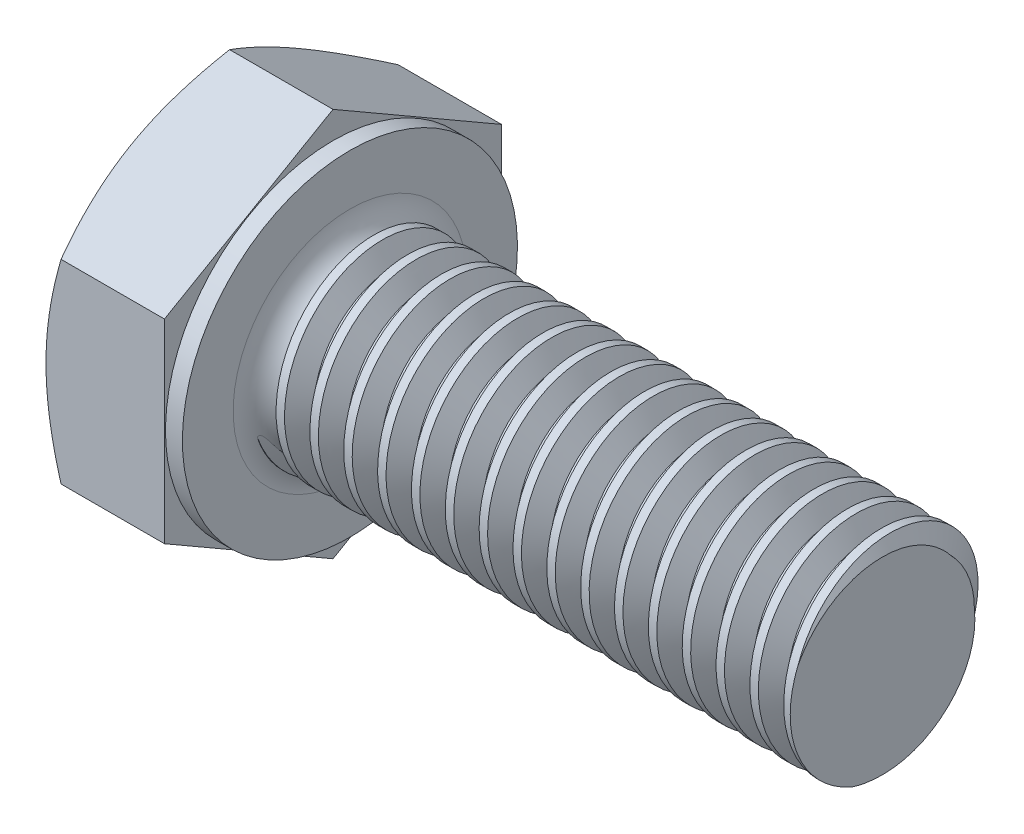
SolidWorks part; units mm, degrees
ref_plane "Front Plane" through (0, 0, 0) normal (0, 0, 1) x (1, 0, 0)
ref_plane "Top Plane" through (0, 0, 0) normal (0, 1, 0) x (1, 0, 0)
ref_plane "Right Plane" through (0, 0, 0) normal (1, 0, 0) x (0, 0, -1)
sketch "Sketch1" plane through (0, 0, 0) normal (0, 0, 1) x (1, 0, 0)
  line L0 (0, 0) -> (-20, 0)
  line L1 (-20, 0) -> (-20, 5.75)
  line L2 (-20, 5.75) -> (-16.5, 5.75)
  line L3 (-16.5, 5.75) -> (-16.5, 4.95)
  line L4 (-16.5, 4.95) -> (-16, 4.95)
  line L5 (-16, 4.95) -> (-16, 3.45)
  line L6 (-15, 2.45) -> (0, 2.45)
  line L7 (0, 2.45) -> (0, 0)
  line L8 (-20, 4.9796) -> (-19.5552, 5.75)
  line L9 (-20, 5.75) -> (-24.9796, 2.875) construction
  line L10 (-24.9796, 2.875) -> (-24.9796, -2.875) construction
  line L11 (-24.9796, -2.875) -> (-20, -5.75) construction
  line L12 (-20, -5.75) -> (-15.0204, -2.875) construction
  line L13 (-15.0204, -2.875) -> (-15.0204, 2.875) construction
  line L14 (-15.0204, 2.875) -> (-20, 5.75) construction
  circle A0 centre (-20, 0) radius 4.9796 construction
  arc A1 (-16, 3.45) -> (-15, 2.45) centre (-15, 3.45) ccw
  point P19 (-16, 2.45)
  dimension "D8" = 1
  dimension "D1" = 2.45
  dimension "D2" = 16
  dimension "D3" = 2.5
  dimension "D4" = 0.5
  dimension "D5" = 3.5
  dimension "D6" = 5.75
  dimension "D7" = 30
revolve "Revolve1" add sketch "Sketch1" angle 360 about L0
sketch "Sketch2" plane through (-20, 0, 0) normal (-1, 0, 0) x (0, 0, 1)
  line L1 (0, 5.75) -> (-4.9796, 2.875)
  line L2 (-4.9796, 2.875) -> (-4.9796, -2.875)
  line L3 (-4.9796, -2.875) -> (0, -5.75)
  line L4 (0, -5.75) -> (4.9796, -2.875)
  line L5 (4.9796, -2.875) -> (4.9796, 2.875)
  line L6 (4.9796, 2.875) -> (0, 5.75)
  circle A0 centre (0, 0) radius 4.9796 construction
  circle A1 centre (0, 0) radius 5.75 construction
extrude "Cut-Extrude1" cut sketch "Sketch2" against normal through all flip side to cut
thread "Thread1" pitch 1 method extrude profile "Thread Profile3" start angle 0, offset 2, length 0, pitch 1, diameter 4.9
ref_plane "Plane3" through (-17, 0, -2.45) normal (0, 1, 0) x (0, 0, 1)
sketch "Thread Profile3" plane through (-17, 0, -2.45) normal (0, 1, 0) x (0, 0, 1)
  line L0 (0, 0) -> (0, 1) construction
  line L11 (0, 0) -> (0, 0.875)
  line L12 (0, 0.875) -> (-0.5413, 0.5625)
  line L13 (-0.5413, 0.5625) -> (-0.5413, 0.3125)
  line L15 (-0.5413, 0.3125) -> (0, 0)
  line L17 (-0.5413, 0.4375) -> (0, 0.4375) construction
  point P2 (0, 0)
  dimension "Pitch" = 1
  dimension "Profile_Angle" = 60
  dimension "Profile_Land" = 0.25
  dimension "Profile_Height" = 0.5413
other "SurfaceCut2" flip cut yes
